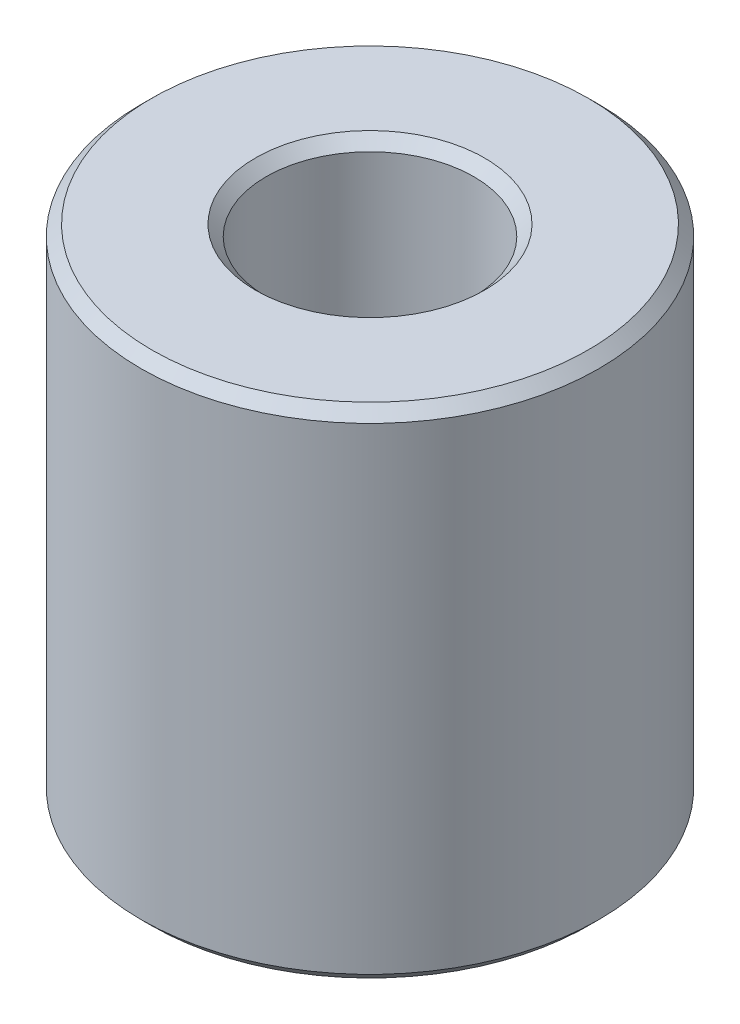
SolidWorks part; units mm, degrees
ref_plane "Front Plane" through (0, 0, 0) normal (0, 0, 1) x (1, 0, 0)
ref_plane "Top Plane" through (0, 0, 0) normal (0, 1, 0) x (1, 0, 0)
ref_plane "Right Plane" through (0, 0, 0) normal (1, 0, 0) x (0, 0, -1)
sketch "Sketch1" plane through (0, 0, 0) normal (0, 1, 0) x (1, 0, 0)
  circle A0 centre (0, 0) radius 25
  dimension "SLEEVE_OD" = 50
extrude "Boss-Extrude1" add sketch "Sketch1" along normal blind 54.4627
sketch "Sketch2" plane through (0, 0, 0) normal (0, 1, 0) x (1, 0, 0)
  circle A0 centre (0, 0) radius 11.3381
  dimension "BORE_D" = 22.6763
extrude "Cut-Extrude1" cut sketch "Sketch2" along normal through all
chamfer "Chamfer1" distance 1.177 angle 45 4 edges at (0, 54.4627, 11.3381) (0, 0, 11.3381) (0, 0, 25) (0, 54.4627, 25)
